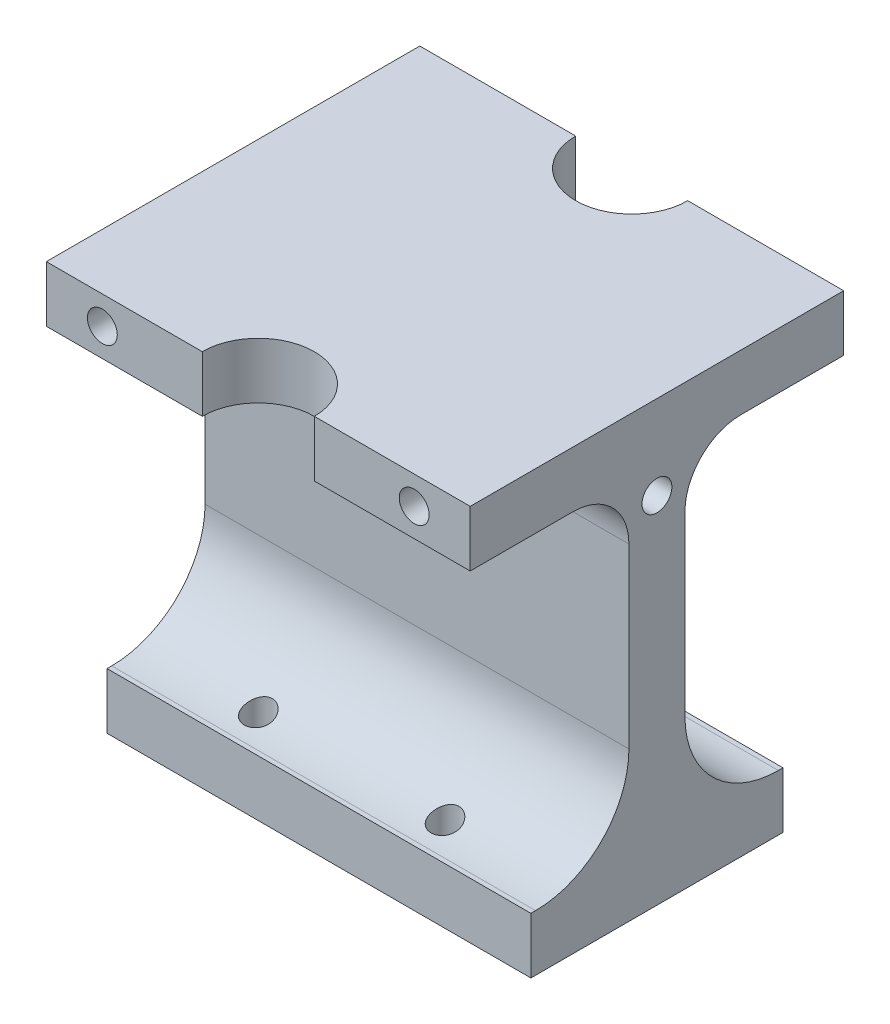
SolidWorks part; units mm, degrees
ref_plane "Płaszczyzna przednia" through (0, 0, 0) normal (0, 0, 1) x (1, 0, 0)
ref_plane "Płaszczyzna górna" through (0, 0, 0) normal (0, 1, 0) x (1, 0, 0)
ref_plane "Płaszczyzna prawa" through (0, 0, 0) normal (1, 0, 0) x (0, 0, -1)
sketch "Sketch1" plane through (0, 0, 0) normal (0, 1, 0) x (1, 0, 0)
  line L1 (0, 0) -> (45.4, 0)
  line L2 (0, 0) -> (0, 27)
  line L3 (0, 27) -> (45.4, 27)
  line L4 (45.4, 0) -> (45.4, 27)
  dimension "D1" = 45.4
  dimension "D2" = 27
extrude "Boss-Extrude1" add sketch "Sketch1" along normal blind 6
sketch "Sketch4" plane through (0, 6, 0) normal (0, 1, 0) x (1, 0, 0)
  line L0 (0, 27) -> (0, 0) construction
  line L1 (0, 16.5) -> (45.4, 16.5)
  line L2 (0, 16.5) -> (0, 10.5)
  line L3 (0, 10.5) -> (45.4, 10.5)
  line L4 (45.4, 16.5) -> (45.4, 10.5)
  line L5 (45.4, 0) -> (45.4, 27) construction
  line L6 (0, 0) -> (45.4, 0) construction
  dimension "D1" = 6
  dimension "D2" = 10.5
extrude "Boss-Extrude2" add sketch "Sketch4" along normal blind 35
fillet "Fillet3" radius 10 2 edges at (22.7, 6, -10.5) (22.7, 6, -16.5)
ref_plane "Plane3" through (0, 16, 0) normal (0, -1, 0) x (-1, 0, 0)
hole_wizard "Ø3.0mm Dowel Hole1" positions "Sketch2" profile "Sketch3" hole size "Ø3.0" standard "ANSI Metric" end condition up to next
sketch "Sketch2" plane through (0, 16, 0) normal (0, 1, 0) x (1, 0, 0)
  point P0 (12.7, 23.5)
  point P2 (32.7, 23.5)
  point P4 (32.7, 3.5)
  point P6 (12.7, 3.5)
  dimension "D1" = 20
  dimension "D2" = 20
  dimension "D3" = 20
sketch "Sketch3" plane through (12.7, 16, -23.5) normal (1, 0, 0) x (0, 0, 1)
  line L0 (0, 0) -> (0, 16)
  line L1 (0, 16) -> (1.5, 16)
  line L2 (1.5, 16) -> (1.5, 0)
  line L5 (1.5, 0) -> (0, 0)
  line L11 (0, -6.35) -> (0, 107.95) construction
  dimension "Thru Hole Dia." = 3
  dimension "Thru Hole Depth" = 16
sketch "Sketch5" plane through (0, 41, 0) normal (0, 1, 0) x (1, 0, 0)
  line L0 (45.4, 13.5) -> (0, 13.5) construction
  line L1 (45.4, 33.5) -> (28.7, 33.5)
  line L2 (45.4, 33.5) -> (45.4, -6.5)
  line L3 (45.4, -6.5) -> (28.7, -6.5)
  line L4 (0, 33.5) -> (0, -6.5)
  line L5 (45.4, 33.5) -> (0, -6.5) construction
  line L6 (45.4, -6.5) -> (0, 33.5) construction
  line L7 (45.4, 10.5) -> (45.4, 16.5) construction
  line L8 (0, 16.5) -> (0, 10.5) construction
  line L9 (16.7, 33.5) -> (0, 33.5)
  line L10 (16.7, -6.5) -> (0, -6.5)
  line L11 (22.7, 33.5) -> (22.7, -6.5) construction
  line L12 (45.4, 33.5) -> (0, 33.5) construction
  line L13 (15.0168, -6.5) -> (31.9525, -6.5) construction
  arc A0 (16.7, 33.5) -> (28.7, 33.5) centre (22.7, 33.5) ccw
  arc A1 (28.7, -6.5) -> (16.7, -6.5) centre (22.7, -6.5) ccw
  point P4 (22.7, 13.5)
  dimension "D2" = 6
  dimension "D3" = 6
  dimension "D4" = 22.7
  dimension "D1" = 40
extrude "Boss-Extrude3" add sketch "Sketch5" along normal blind 6
fillet "Fillet4" radius 6 2 edges at (22.7, 41, -10.5) (22.7, 41, -16.5)
hole_wizard "Ø3.2 (3.2) Diameter Hole1" positions "Sketch6" profile "Sketch7" hole size "Ø3.2" standard "ANSI Metric"
sketch "Sketch6" plane through (0, 0, 6.5) normal (0, 0, 1) x (1, 0, 0)
  line L0 (0, 47) -> (0, 41) construction
  line L1 (0, 41) -> (16.7, 41) construction
  line L2 (45.4, 47) -> (45.4, 41) construction
  point P0 (6, 44)
  point P2 (39.4, 44)
  dimension "D1" = 6
  dimension "D2" = 3
  dimension "D3" = 6
sketch "Sketch7" plane through (6, 44, 6.5) normal (1, 0, 0) x (0, -1, 0)
  line L0 (0, 0) -> (0, 6.9614)
  line L1 (0, 6.9614) -> (1.6, 6)
  line L2 (1.6, 6) -> (1.6, 0)
  line L5 (1.6, 0) -> (0, 0)
  line L10 (0, 6.9614) -> (-1.6, 6) construction
  line L11 (0, -6.35) -> (0, 107.95) construction
  dimension "Hole Dia." = 3.2
  dimension "Hole Depth" = 6
  dimension "Drill Angle" = 118
hole_wizard "Ø3.2 (3.2) Diameter Hole2" positions "Sketch8" profile "Sketch9" hole size "Ø3.2" standard "ANSI Metric"
sketch "Sketch8" plane through (0, 0, -33.5) normal (0, 0, -1) x (-1, 0, 0)
  line L0 (-45.4, 47) -> (-28.7, 47) construction
  line L2 (-45.4, 47) -> (-45.4, 41) construction
  line L3 (0, 47) -> (0, 41) construction
  point P0 (-39.4, 44)
  point P2 (-6, 44)
  dimension "D1" = 3
  dimension "D2" = 6
  dimension "D3" = 6
sketch "Sketch9" plane through (39.4, 44, -33.5) normal (1, 0, 0) x (0, 1, 0)
  line L0 (0, 0) -> (0, 6.9614)
  line L1 (0, 6.9614) -> (1.6, 6)
  line L2 (1.6, 6) -> (1.6, 0)
  line L5 (1.6, 0) -> (0, 0)
  line L10 (0, 6.9614) -> (-1.6, 6) construction
  line L11 (0, -6.35) -> (0, 107.95) construction
  dimension "Hole Dia." = 3.2
  dimension "Hole Depth" = 6
  dimension "Drill Angle" = 118
hole_wizard "Ø3.2 (3.2) Diameter Hole3" positions "Sketch10" profile "Sketch12" hole size "Ø3.2" standard "ANSI Metric"
sketch "Sketch10" plane through (45.4, 0, 0) normal (1, 0, 0) x (0, 0, -1)
  point P0 (13.5, 38)
sketch "Sketch12" plane through (45.4, 38, -13.5) normal (0, 1, 0) x (0, 0, -1)
  line L0 (0, 0) -> (0, 12.9614)
  line L1 (0, 12.9614) -> (1.6, 12)
  line L2 (1.6, 12) -> (1.6, 0)
  line L5 (1.6, 0) -> (0, 0)
  line L10 (0, 12.9614) -> (-1.6, 12) construction
  line L11 (0, -6.35) -> (0, 107.95) construction
  dimension "Hole Dia." = 3.2
  dimension "Hole Depth" = 12
  dimension "Drill Angle" = 118
